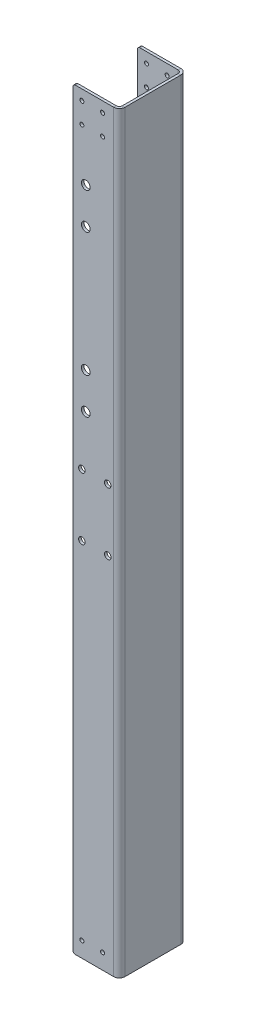
SolidWorks part; units mm, degrees
note: The reader was unsure of these and kept them because the rebuilt part matched: flange length of "Edge-Flange1", "Edge-Flange2".
material "5052-H32"
ref_plane "Front Plane" through (0, 0, 0) normal (0, 0, 1) x (1, 0, 0)
ref_plane "Top Plane" through (0, 0, 0) normal (0, 1, 0) x (1, 0, 0)
ref_plane "Right Plane" through (0, 0, 0) normal (1, 0, 0) x (0, 0, -1)
sketch "Sketch1" plane through (0, 0, 0) normal (1, 0, 0) x (0, 0, -1)
  line L1 (0, 0) -> (76.2, 0)
  line L2 (0, 0) -> (0, 925.5125)
  line L3 (0, 925.5125) -> (76.2, 925.5125)
  line L4 (76.2, 0) -> (76.2, 925.5125)
  dimension "D1" = 925.5125
  dimension "D2" = 76.2
base flange "Base-Flange1" sketch "Sketch1" thickness 3.175 reverse thickness direction no parameters "D1"=3.81
edge flange "Edge-Flange1" sketch "Sketch8" flange angle 90 flange length 57.15 flange position material outside bend radius 3.81 thickness 3.175 relief rectangular parameters "D6"=10
sketch "Sketch8" plane through (-3.175, 0, 0) normal (0, 0, -1) x (0, -1, 0)
  line L2 (-925.5125, 0) -> (-925.5125, 53.975)
  line L3 (-925.5125, 53.975) -> (0, 53.975)
  line L4 (0, 53.975) -> (0, 0)
  line L5 (0, 0) -> (-925.5125, 0) construction
  line L6 (0, 0) -> (-925.5125, 0)
bend "EdgeBend1" bend radius 3.81 bend angle 90 parameters "D5"=1
edge flange "Edge-Flange2" sketch "Sketch11" flange angle 90 flange length 57.15 flange position material outside bend radius 3.81 thickness 3.175 relief rectangular parameters "D6"=10
sketch "Sketch11" plane through (-3.175, 0, -76.2) normal (0, 0, 1) x (0, 1, 0)
  line L2 (0, 0) -> (0, 53.975)
  line L3 (0, 53.975) -> (925.5125, 53.975)
  line L4 (925.5125, 53.975) -> (925.5125, 0)
  line L9 (925.5125, 0) -> (0, 0) construction
  line L10 (925.5125, 0) -> (0, 0)
bend "EdgeBend2" bend radius 3.81 bend angle 90 parameters "D5"=2
hole_wizard "#10 (0.1935) Diameter Hole2" positions "Sketch12" profile "Sketch13" hole size "#10" standard "ANSI Inch" end condition through all
sketch "Sketch12" plane through (0, 0, -79.375) normal (0, 0, -1) x (-1, 0, 0)
  line L2 (57.15, 925.5125) -> (57.15, 0) construction
  line L3 (57.15, 0) -> (6.985, 0) construction
  point P0 (20.6375, 19.05)
  point P2 (46.0375, 19.05)
  dimension "D1" = 11.1125
  dimension "D2" = 25.4
  dimension "D3" = 19.05
sketch "Sketch13" plane through (-20.6375, 19.05, -79.375) normal (1, 0, 0) x (0, 1, 0)
  line L0 (0, 0) -> (0, 82.55)
  line L1 (0, 82.55) -> (2.4574, 82.55)
  line L2 (2.4574, 82.55) -> (2.4574, 0)
  line L5 (2.4574, 0) -> (0, 0)
  line L11 (0, -6.35) -> (0, 107.95) construction
  dimension "Thru Hole Dia." = 4.9149
  dimension "Thru Hole Depth" = 82.55
hole_wizard "#10 (0.1935) Diameter Hole1" positions "Sketch14" profile "Sketch15" hole size "#10" standard "ANSI Inch" end condition through all
sketch "Sketch14" plane through (0, 0, -79.375) normal (0, 0, -1) x (-1, 0, 0)
  line L0 (57.15, 925.5125) -> (57.15, 0) construction
  line L1 (6.985, 925.5125) -> (57.15, 925.5125) construction
  point P0 (46.0375, 912.8125)
  point P2 (20.6375, 912.8125)
  point P4 (20.6375, 887.4125)
  point P6 (46.0375, 887.4125)
  dimension "D1" = 11.1125
  dimension "D2" = 25.4
  dimension "D3" = 12.7
  dimension "D4" = 25.4
sketch "Sketch15" plane through (-46.0375, 912.8125, -79.375) normal (1, 0, 0) x (0, 1, 0)
  line L0 (0, 0) -> (0, 82.55)
  line L1 (0, 82.55) -> (2.4574, 82.55)
  line L2 (2.4574, 82.55) -> (2.4574, 0)
  line L5 (2.4574, 0) -> (0, 0)
  line L11 (0, -6.35) -> (0, 107.95) construction
  dimension "Thru Hole Dia." = 4.9149
  dimension "Thru Hole Depth" = 82.55
fillet "Fillet1" radius 3.175 4 edges at (-57.15, 0, 1.5875) (-57.15, 0, -77.7875) (-57.15, 925.5125, 1.5875) (-57.15, 925.5125, -77.7875)
hole_wizard "O (0.316) Diameter Hole1" positions "Sketch16" profile "Sketch17" hole size "O" standard "ANSI Inch" end condition through all
sketch "Sketch16" plane through (0, 0, -79.375) normal (0, 0, -1) x (-1, 0, 0)
  line L0 (0, 0) -> (0, 925.5125) construction
  line L1 (53.975, 0) -> (6.985, 0) construction
  point P0 (14.2875, 520.7)
  point P2 (14.2875, 444.5)
  point P4 (46.0375, 520.7)
  point P6 (46.0375, 444.5)
  dimension "D1" = 14.2875
  dimension "D2" = 31.75
  dimension "D3" = 444.5
  dimension "D4" = 520.7
sketch "Sketch17" plane through (-14.2875, 520.7, -79.375) normal (1, 0, 0) x (0, 1, 0)
  line L0 (0, 0) -> (0, 82.55)
  line L1 (0, 82.55) -> (4.0132, 82.55)
  line L2 (4.0132, 82.55) -> (4.0132, 0)
  line L5 (4.0132, 0) -> (0, 0)
  line L11 (0, -6.35) -> (0, 107.95) construction
  dimension "Thru Hole Dia." = 8.0264
  dimension "Thru Hole Depth" = 82.55
hole_wizard "27/64 (0.42188) Diameter Hole1" positions "Sketch18" profile "Sketch19" hole size "27/64" standard "ANSI Inch" end condition through all
sketch "Sketch18" plane through (0, 0, 3.175) normal (0, 0, 1) x (1, 0, 0)
  point P0 (-41.275, 825.5)
  point P2 (-41.275, 781.05)
  point P4 (-41.275, 628.65)
  point P6 (-41.275, 584.2)
sketch "Sketch19" plane through (-41.275, 825.5, 3.175) normal (1, 0, 0) x (0, -1, 0)
  line L0 (0, 0) -> (0, 82.55)
  line L1 (0, 82.55) -> (5.3579, 82.55)
  line L2 (5.3579, 82.55) -> (5.3579, 0)
  line L5 (5.3579, 0) -> (0, 0)
  line L11 (0, -6.35) -> (0, 107.95) construction
  dimension "Thru Hole Dia." = 10.7158
  dimension "Thru Hole Depth" = 82.55
sketch "Bend-Lines1" [suppressed] plane through (0, 0, 0) normal (0, 1, 0) x (1, 0, 0)
sketch "Bounding-Box1" [suppressed] plane through (0, 0, 0) normal (0, 1, 0) x (1, 0, 0)
sheet metal parameters "Sheet-Metal1" thickness 3.175 parameters "D1"=3
flat pattern "Flat-Pattern1" [suppressed]
sketch "Bend-Lines2" plane through (0, 0, 0) normal (0, 1, 0) x (1, 0, 0)
sketch3d "Bounding-Box2" [suppressed]
  line L0 (0, 914.4, 0) -> (0, 0, 0) construction
  line L1 (-76.2, 914.4, 0) -> (-76.2, 0, 0) construction
  line L2 (0, 914.4, 0) -> (-76.2, 914.4, 0) construction
  line L3 (0, 0, 0) -> (-76.2, 0, 0) construction
sheet metal parameters "Sheet-Metal2" thickness 3.175 parameters "D1"=3
flat pattern "Flat-Pattern1"
sketch "Bend-Lines2" plane through (0, 0, 0) normal (1, 0, 0) x (0, 0, -1)
  line L0 (-0.603, 914.4) -> (-0.603, 0) construction
  line L1 (-0.603, 914.4) -> (-0.603, 0) construction
sketch3d "Bounding-Box2" [suppressed]
  line L0 (-55.181, 914.4, 0) -> (-55.181, 0, 0) construction
  line L1 (76.2, 914.4, 0) -> (76.2, 0, 0) construction
  line L2 (-55.181, 914.4, 0) -> (76.2, 914.4, 0) construction
  line L3 (-55.181, 0, 0) -> (76.2, 0, 0) construction
bend of the flat pattern "Flatten-<EdgeBend1>1"
sheet metal parameters "Sheet-Metal3" thickness 3.175 parameters "D1"=3
flat pattern "Flat-Pattern1"
sketch "Bend-Lines2" plane through (0, 0, 0) normal (1, 0, 0) x (0, 0, -1)
  line L0 (-0.4292, 914.4) -> (-0.4292, 0) construction
  line L1 (-0.4292, 914.4) -> (-0.4292, 0) construction
  line L2 (76.6292, 0) -> (76.6292, 914.4) construction
  line L3 (76.6292, 0) -> (76.6292, 914.4) construction
sketch3d "Bounding-Box2" [suppressed]
  line L0 (-54.8334, 914.4, 0) -> (-54.8334, 0, 0) construction
  line L1 (131.0334, 914.4, 0) -> (131.0334, 0, 0) construction
  line L2 (-54.8334, 914.4, 0) -> (131.0334, 914.4, 0) construction
  line L3 (-54.8334, 0, 0) -> (131.0334, 0, 0) construction
bend of the flat pattern "Flatten-<EdgeBend1>1"
bend of the flat pattern "Flatten-<EdgeBend2>1"
sheet metal parameters "Sheet-Metal4" thickness 3.175 parameters "D1"=3
flat pattern "Flat-Pattern1"
sketch "Bend-Lines2" plane through (0, 0, 0) normal (1, 0, 0) x (0, 0, -1)
  line L0 (-0.4292, 914.4) -> (-0.4292, 0) construction
  line L1 (-0.4292, 914.4) -> (-0.4292, 0) construction
  line L2 (76.6292, 0) -> (76.6292, 914.4) construction
  line L3 (76.6292, 0) -> (76.6292, 914.4) construction
sketch3d "Bounding-Box2" [suppressed]
  line L0 (-54.8334, 914.4, 0) -> (-54.8334, 0, 0) construction
  line L1 (131.0334, 914.4, 0) -> (131.0334, 0, 0) construction
  line L2 (-54.8334, 914.4, 0) -> (131.0334, 914.4, 0) construction
  line L3 (-54.8334, 0, 0) -> (131.0334, 0, 0) construction
bend of the flat pattern "Flatten-<EdgeBend1>1"
bend of the flat pattern "Flatten-<EdgeBend2>1"
sheet metal parameters "Sheet-Metal5" thickness 3.175 parameters "D1"=3
flat pattern "Flat-Pattern1"
sketch "Bend-Lines2" plane through (0, 0, 0) normal (1, 0, 0) x (0, 0, -1)
  line L0 (-0.4292, 914.4) -> (-0.4292, 0) construction
  line L1 (-0.4292, 914.4) -> (-0.4292, 0) construction
  line L2 (76.6292, 0) -> (76.6292, 914.4) construction
  line L3 (76.6292, 0) -> (76.6292, 914.4) construction
sketch3d "Bounding-Box2" [suppressed]
  line L0 (-54.8334, 914.4, 0) -> (-54.8334, 0, 0) construction
  line L1 (131.0334, 914.4, 0) -> (131.0334, 0, 0) construction
  line L2 (-54.8334, 914.4, 0) -> (131.0334, 914.4, 0) construction
  line L3 (-54.8334, 0, 0) -> (131.0334, 0, 0) construction
bend of the flat pattern "Flatten-<EdgeBend1>1"
bend of the flat pattern "Flatten-<EdgeBend2>1"
sheet metal parameters "Sheet-Metal6" thickness 3.175 parameters "D1"=3
flat pattern "Flat-Pattern1"
sketch "Bend-Lines2" plane through (0, 0, 0) normal (1, 0, 0) x (0, 0, -1)
  line L0 (-0.4292, 925.5125) -> (-0.4292, 0) construction
  line L1 (-0.4292, 925.5125) -> (-0.4292, 0) construction
  line L2 (76.6292, 0) -> (76.6292, 925.5125) construction
  line L3 (76.6292, 0) -> (76.6292, 925.5125) construction
sketch3d "Bounding-Box2" [suppressed]
  line L0 (-54.8334, 925.5125, 0) -> (-54.8334, 0, 0) construction
  line L1 (131.0334, 925.5125, 0) -> (131.0334, 0, 0) construction
  line L2 (-54.8334, 925.5125, 0) -> (131.0334, 925.5125, 0) construction
  line L3 (-54.8334, 0, 0) -> (131.0334, 0, 0) construction
bend of the flat pattern "Flatten-<EdgeBend1>1"
bend of the flat pattern "Flatten-<EdgeBend2>1"
sheet metal parameters "Sheet-Metal7" thickness 3.175 parameters "D1"=3
flat pattern "Flat-Pattern1"
sketch "Bend-Lines2" plane through (0, 0, 0) normal (1, 0, 0) x (0, 0, -1)
  line L0 (-0.509, 925.5125) -> (-0.509, 0) construction
  line L1 (-0.509, 925.5125) -> (-0.509, 0) construction
  line L2 (76.709, 0) -> (76.709, 925.5125) construction
  line L3 (76.709, 0) -> (76.709, 925.5125) construction
sketch3d "Bounding-Box2" [suppressed]
  line L0 (-54.993, 925.5125, 0) -> (-54.993, 0, 0) construction
  line L1 (131.193, 925.5125, 0) -> (131.193, 0, 0) construction
  line L2 (-54.993, 925.5125, 0) -> (131.193, 925.5125, 0) construction
  line L3 (-54.993, 0, 0) -> (131.193, 0, 0) construction
bend of the flat pattern "Flatten-<EdgeBend1>1"
bend of the flat pattern "Flatten-<EdgeBend2>1"
